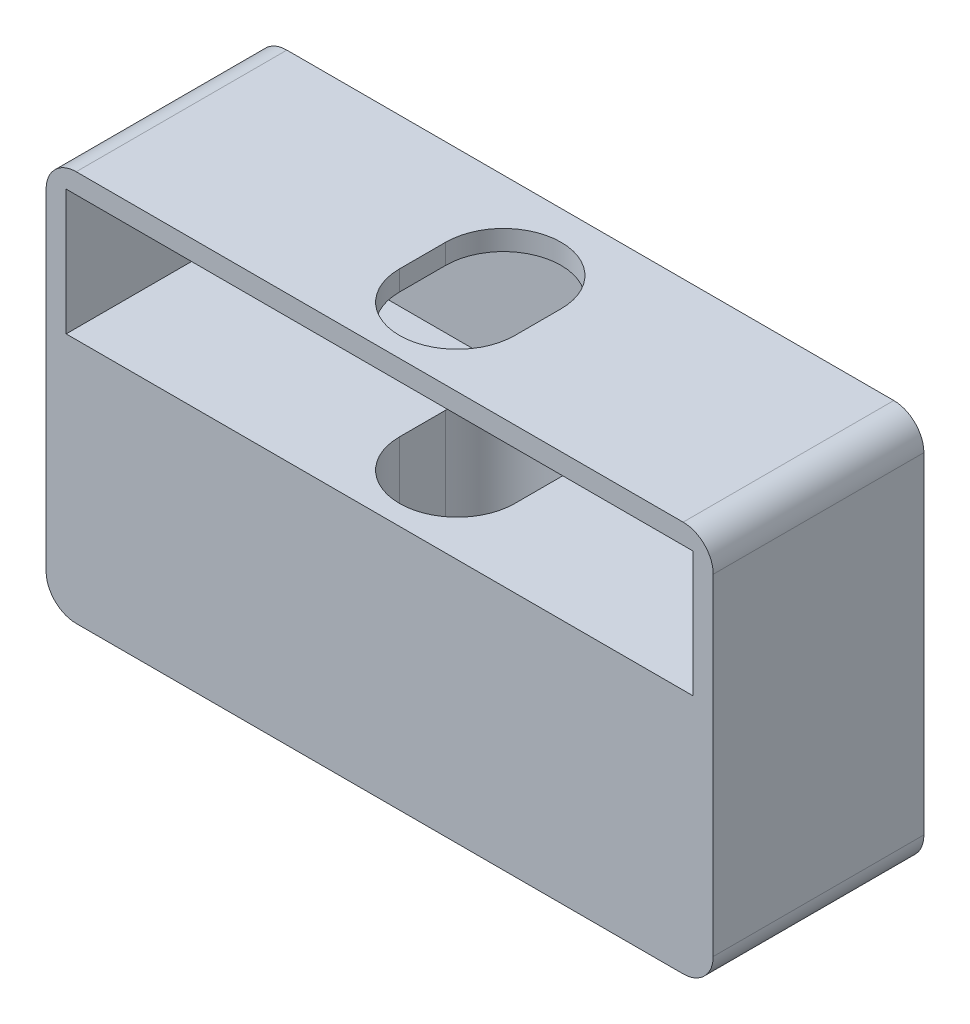
SolidWorks part; units mm, degrees
ref_plane "Front Plane" through (0, 0, 0) normal (0, 0, 1) x (1, 0, 0)
ref_plane "Top Plane" through (0, 0, 0) normal (0, 1, 0) x (1, 0, 0)
ref_plane "Right Plane" through (0, 0, 0) normal (1, 0, 0) x (0, 0, -1)
sketch "Sketch1" plane through (0, 0, 0) normal (0, 0, 1) x (1, 0, 0)
  line L1 (-6.25, 1.25) -> (6.25, 1.25)
  line L2 (-6.25, 1.25) -> (-6.25, -1.25)
  line L3 (-6.25, -1.25) -> (6.25, -1.25)
  line L4 (6.25, 1.25) -> (6.25, -1.25)
  line L5 (-6.25, 1.25) -> (6.25, -1.25) construction
  line L6 (-6.25, -1.25) -> (6.25, 1.25) construction
  point P0 (0, 0)
  dimension "D1" = 12.5
  dimension "D2" = 2.5
extrude "Boss-Extrude1" add sketch "Sketch1" along normal blind 0.4
extrude "Extrude-Thin1" add sketch "Sketch1<3>" along normal blind 4.2 thin contours L1 L4 L3 L2 thin type one direction wall 0.4
sketch "Sketch1<3>" plane through (0, 0, 0) normal (0, 0, 1) x (1, 0, 0) same geometry as "Sketch1"
sketch "Sketch2" plane through (0, -1.65, 0) normal (0, -1, 0) x (1, 0, 0)
  line L4 (-6.65, 0) -> (6.65, 0)
  line L5 (6.65, 0) -> (6.65, 4.2)
  line L6 (6.65, 4.2) -> (-6.65, 4.2)
  line L7 (-6.65, 4.2) -> (-6.65, 0)
  line L8 (-6.65, 0) -> (6.65, 0)
  line L9 (6.65, 0) -> (6.65, 4.2)
  line L10 (6.65, 4.2) -> (-6.65, 4.2)
  line L11 (-6.65, 4.2) -> (-6.65, 0)
  dimension "D1" = 0
extrude "Boss-Extrude2" add sketch "Sketch2" along normal blind 4.5
sketch "Sketch3" plane through (0, 1.65, 0) normal (0, 1, 0) x (1, 0, 0)
  line L0 (0, -1.7335) -> (0, -2.655) construction
  line L1 (1.15, -1.7335) -> (1.15, -2.655)
  line L2 (-1.15, -1.7335) -> (-1.15, -2.655)
  arc A1 (1.15, -1.7335) -> (-1.15, -1.7335) centre (0, -1.7335) ccw
  arc A2 (-1.15, -2.655) -> (1.15, -2.655) centre (0, -2.655) ccw
  point P2 (0, -2.1942)
  dimension "D1" = 1.15
extrude "Cut-Extrude1" cut sketch "Sketch3" against normal through all
fillet "Fillet1" radius 0.6 4 edges at (6.65, -6.15, 2.1) (6.65, 1.65, 2.1) (-6.65, 1.65, 2.1) (-6.65, -6.15, 2.1)
